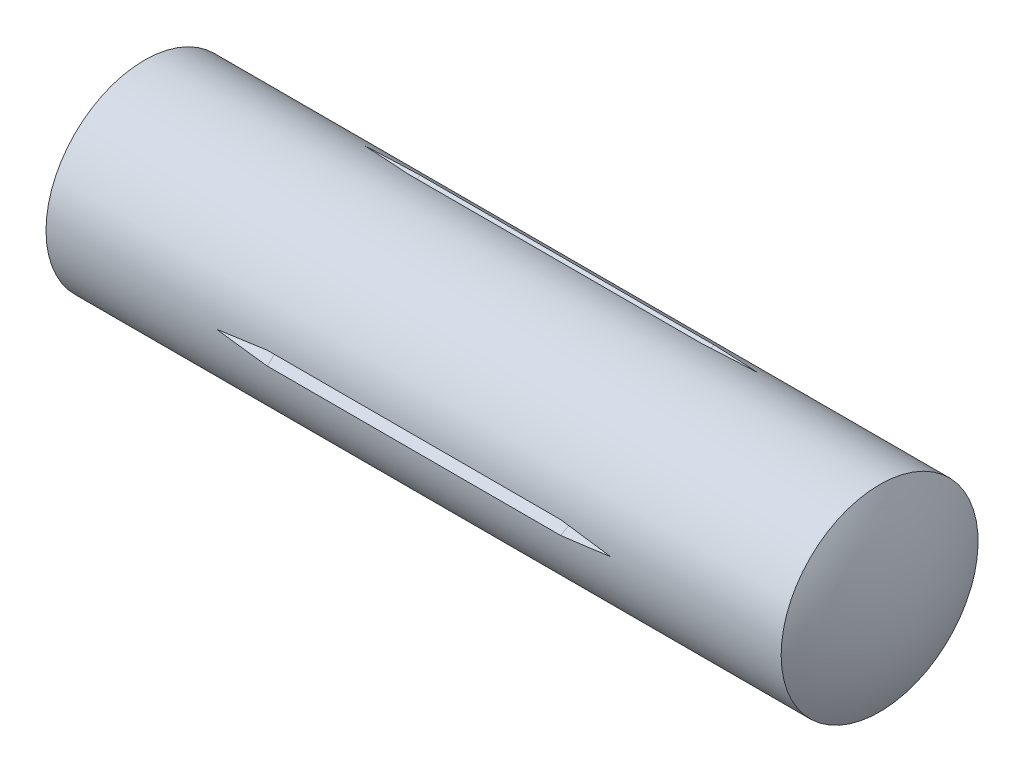
SolidWorks part; units mm, degrees
ref_plane "Plane1" through (0, 0, 0) normal (0, 0, 1) x (1, 0, 0)
ref_plane "Plane2" through (0, 0, 0) normal (0, 1, 0) x (1, 0, 0)
ref_plane "Plane3" through (0, 0, 0) normal (1, 0, 0) x (0, 0, -1)
sketch "Sketch1" plane through (0, 0, 0) normal (0, 0, 1) x (1, 0, 0)
  line L0 (-57, 0) -> (60, 0) construction
  line L1 (-50, 0) -> (-50, 1.25)
  line L2 (-46.6819, 12.5) -> (46.6506, 12.5)
  line L3 (-50, 0) -> (50, 0)
  arc A0 (-46.6819, 12.5) -> (-50, 1.25) centre (-25.0313, 0) ccw
  arc A1 (50, 0) -> (46.6506, 12.5) centre (25, 0) ccw
  dimension "D1" = 25
  dimension "D2" = 25
  dimension "Length" = 100
  dimension "D3" = 2.5
revolve "Base-Revolve" add sketch "Sketch1" angle 360 about L0
sketch "Sketch3" plane through (0, 0, 0) normal (0, 1, 0) x (1, 0, 0)
  line L0 (0, 0) -> (60, 0) construction
  line L1 (-57, 0) -> (60, 0) construction
  line L2 (-25, -12.5) -> (-18.75, -11.25)
  line L3 (-18.75, -11.25) -> (18.75, -11.25)
  line L4 (18.75, -11.25) -> (25, -12.5)
  dimension "D1" = 25
  dimension "D2" = 50
  dimension "D3" = 25
  dimension "D4" = 22.5
  dimension "D5" = 6.25
  dimension "D6" = 6.25
ref_plane "Plane4" through (-25, 0, 0) normal (1, 0, 0) x (0, 0, -1)
sketch "Sketch4" plane through (-25, 0, 0) normal (1, 0, 0) x (0, 0, -1)
  line L0 (0, 0) -> (-14, 0) construction
  line L1 (-12.5, 0) -> (-14.3784, 1.3152)
  line L2 (-12.5, 0) -> (-14.3784, -1.3152)
  line L3 (-14.3784, -1.3152) -> (-14.3784, 1.3152)
  circle A0 centre (0, 0) radius 12.5 construction
  dimension "D1" = 25
  dimension "D2" = 70
  dimension "D3" = 35
  dimension "D4" = 1.8784
sweep "Cut-Sweep3" cut profiles "Sketch4" path "Sketch3"
pattern_circular "CirPattern2" count 3 over 360 about axis through (-57, 0, 0) along (1, 0, 0) of "Cut-Sweep3"
equation "\"D1@Sketch1\" = \"Diameter@Sketch1\""
equation "\"D2@Sketch1\" = \"Diameter@Sketch1\""
equation "\"D3@Sketch1\" = \"Diameter@Sketch1\" * .1"
equation "\"D1@Sketch3\" = \"Diameter@Sketch1\""
equation "\"D2@Sketch3\" = \"Length@Sketch1\" / 2"
equation "\"D3@Sketch3\" = \"D2@Sketch3\" / 2"
equation "\"D4@Sketch3\" = \"Diameter@Sketch1\" * .9"
equation "\"D5@Sketch3\" = \"D1@Sketch1\" / 4"
equation "\"D6@Sketch3\" = \"D5@Sketch3\""
equation "\"D1@Plane4\" = \"D3@Sketch3\""
equation "\"D1@Sketch4\" = \"Diameter@Sketch1\""
equation "\"D3@Sketch4\" = \"D2@Sketch4\" / 2"
